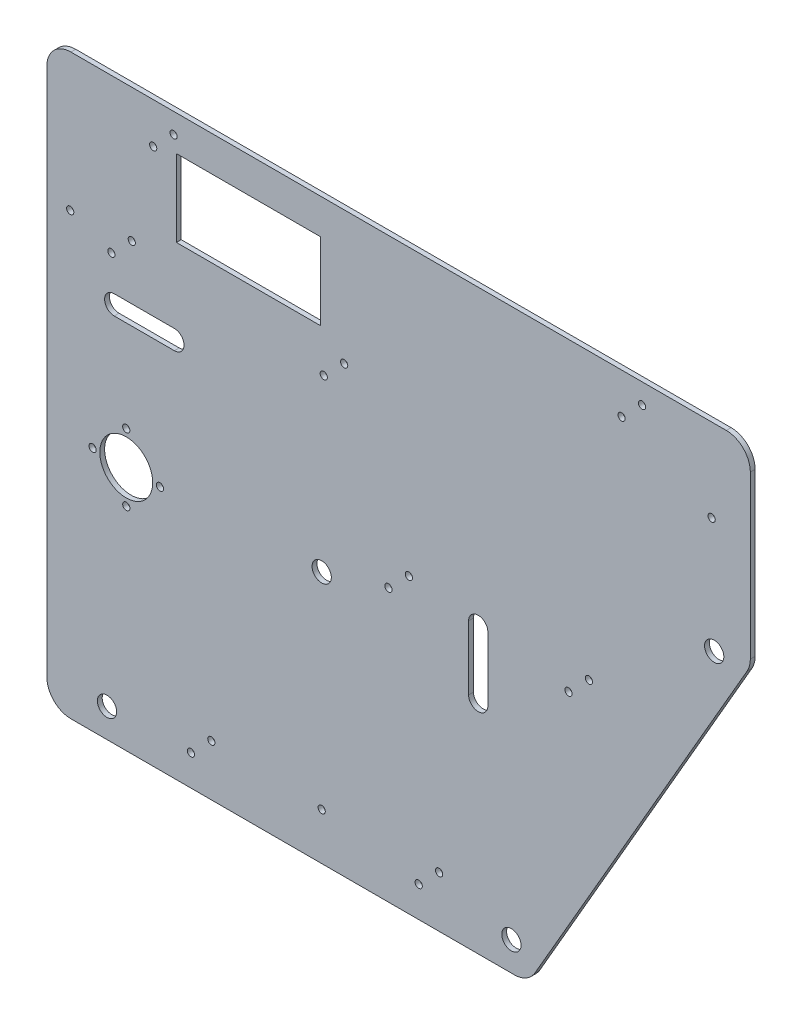
SolidWorks part; units mm, degrees
ref_plane "Front Plane" through (0, 0, 0) normal (0, 0, 1) x (1, 0, 0)
ref_plane "Top Plane" through (0, 0, 0) normal (0, 1, 0) x (1, 0, 0)
ref_plane "Right Plane" through (0, 0, 0) normal (1, 0, 0) x (0, 0, -1)
sketch "Sketch1" plane through (0, 0, 0) normal (0, 0, 1) x (1, 0, 0)
  line L0 (100, 80) -> (192.376, 80)
  line L1 (-100, -80) -> (100, -80)
  line L2 (-100, -80) -> (-100, 80)
  line L3 (-100, 80) -> (100, 80)
  line L4 (100, -80) -> (100, 80)
  line L5 (-100, -80) -> (100, 80) construction
  line L6 (-100, 80) -> (100, -80) construction
  line L7 (192.376, 80) -> (100, -80)
  line L8 (100, 80) -> (100, -80)
  line L10 (-100, 80) -> (192.376, 80)
  line L11 (-100, 80) -> (-100, 110)
  line L12 (-100, 110) -> (192.376, 110)
  line L13 (192.376, 80) -> (192.376, 110)
  point P0 (0, 0)
  dimension "D1" = 160
  dimension "D2" = 200
  dimension "D3" = 30
  dimension "D4" = 30
extrude "Boss-Extrude1" add sketch "Sketch1" along normal blind 2 contours L1 L4 L3 L2 | L7 L0 L4 | L11 L10 L13 L12 region at (0, 0, 0) region at (130.792, 26.6667, 0)
sketch "Sketch2" plane through (0, 0, 2) normal (0, 0, 1) x (1, 0, 0)
  line L0 (-100, -80) -> (100, -80) construction
  line L1 (192.376, 80) -> (100, -80) construction
  line L2 (79.2904, 11.2418) -> (79.2904, 37.9086) construction
  line L3 (-100, -80) -> (-100, 110) construction
  line L4 (-72, 78) -> (-47, 78) construction
  line L7 (-100, 110) -> (192.376, 110) construction
  line L8 (75.2904, 11.2418) -> (75.2904, 37.9086)
  line L9 (-72, 82) -> (-47, 82)
  line L10 (-72, 74) -> (-47, 74)
  line L11 (-100, -80) -> (-100, 110) construction
  line L12 (83.2904, 11.2418) -> (83.2904, 37.9086)
  circle A0 centre (93.0718, -68) radius 4
  circle A1 centre (177.3649, 78) radius 4
  circle A2 centre (-67, 22) radius 11
  circle A3 centre (-75, -68) radius 4
  circle A4 centre (-53, 22) radius 1.5
  circle A5 centre (-67, 36) radius 1.5
  circle A6 centre (-81, 22) radius 1.5
  circle A7 centre (-67, 8) radius 1.5
  circle A11 centre (54.5495, -67.2426) radius 1.5
  circle A12 centre (63.0348, -58.7574) radius 1.5
  circle A13 centre (14.2259, -60.5) radius 1.5
  circle A14 centre (-40.1271, -67.2426) radius 1.5
  circle A15 centre (-31.6419, -58.7574) radius 1.5
  circle A16 centre (-90.2956, 102.8814) radius 1.5
  circle A17 centre (-73.1863, 96.1388) radius 1.5
  circle A18 centre (-64.701, 104.6241) radius 1.5
  circle A19 centre (15.0782, 96.1388) radius 1.5
  circle A20 centre (23.5635, 104.6241) radius 1.5
  circle A21 centre (41.9695, 33.1388) radius 1.5
  circle A22 centre (50.4548, 41.6241) radius 1.5
  circle A23 centre (-39.813, 33.1388) radius 1.5 construction
  circle A24 centre (-31.3277, 41.6241) radius 1.5 construction
  circle A25 centre (116.8113, 33.1388) radius 1.5
  circle A26 centre (125.2966, 41.6241) radius 1.5
  circle A27 centre (79.2904, 25) radius 4 construction
  circle A28 centre (14.2259, 25) radius 4
  arc A29 (-72, 82) -> (-72, 74) centre (-72, 78) ccw
  arc A30 (-47, 74) -> (-47, 82) centre (-47, 78) ccw
  circle A31 centre (176.3056, 125.4889) radius 1.5
  arc A32 (75.2904, 11.2418) -> (83.2904, 11.2418) centre (79.2904, 11.2418) ccw
  arc A33 (83.2904, 37.9086) -> (75.2904, 37.9086) centre (79.2904, 37.9086) ccw
  circle A34 centre (-55.8147, 143.1388) radius 1.5
  circle A35 centre (-47.3294, 151.6241) radius 1.5
  circle A36 centre (138.8916, 143.1388) radius 1.5
  circle A37 centre (147.3769, 151.6241) radius 1.5
  point P26 (-59.5, 78)
  point P87 (79.2904, 24.5752)
  dimension "D3" = 8
  dimension "D4" = 8
  dimension "D9" = 22
  dimension "D10" = 8
  dimension "D12" = 3
  dimension "D13" = 3
  dimension "D14" = 3
  dimension "D15" = 3
  dimension "D16" = 14
  dimension "D20" = 8
  dimension "D22" = 4
  dimension "D25" = 3
  dimension "D26" = 3
  dimension "D29" = 8
  dimension "D28" = 3
  dimension "D1" = 12
  dimension "D2" = 12
  dimension "D5" = 32
  dimension "D6" = 12
  dimension "D7" = 88
  dimension "D8" = 33
  dimension "D11" = 12
  dimension "D17" = 14
  dimension "D18" = 14
  dimension "D19" = 14
  dimension "D21" = 85
  dimension "D23" = 28
  dimension "D24" = 25
  dimension "D27" = 25
  dimension "D30" = 8
extrude "Cut-Extrude1" cut sketch "Sketch2" against normal blind 3
sketch "Sketch4" plane through (0, 0, 2) normal (0, 0, 1) x (1, 0, 0)
  line L0 (192.376, 80) -> (192.376, 110) construction
  line L1 (-100, 110) -> (192.376, 110)
  line L2 (-100, 110) -> (-100, 160)
  line L3 (-100, 160) -> (192.376, 160)
  line L4 (192.376, 110) -> (192.376, 160)
  dimension "D1" = 50
extrude "Boss-Extrude2" add sketch "Sketch4" against normal blind 2
fillet "Fillet1" radius 10 5 edges at (192.376, 160, 1) (192.376, 80, 1) (100, -80, 1) (-100, -80, 1) (-100, 160, 1)
sketch "Sketch5" plane through (0, 0, 2) normal (0, 0, 1) x (1, 0, 0)
  line L1 (-46.1781, 113.3814) -> (13.8219, 113.3814)
  line L2 (-46.1781, 113.3814) -> (-46.1781, 145.3814)
  line L3 (-46.1781, 145.3814) -> (13.8219, 145.3814)
  line L4 (13.8219, 113.3814) -> (13.8219, 145.3814)
  circle A2 centre (-55.8147, 143.1388) radius 1.5
  circle A3 centre (-47.3294, 151.6241) radius 1.5
  circle A4 centre (138.8916, 143.1388) radius 1.5
  circle A5 centre (147.3769, 151.6241) radius 1.5
  circle A6 centre (176.3056, 125.4889) radius 1.5
  dimension "D1" = 3
extrude "Cut-Extrude2" cut sketch "Sketch5" against normal blind 11
